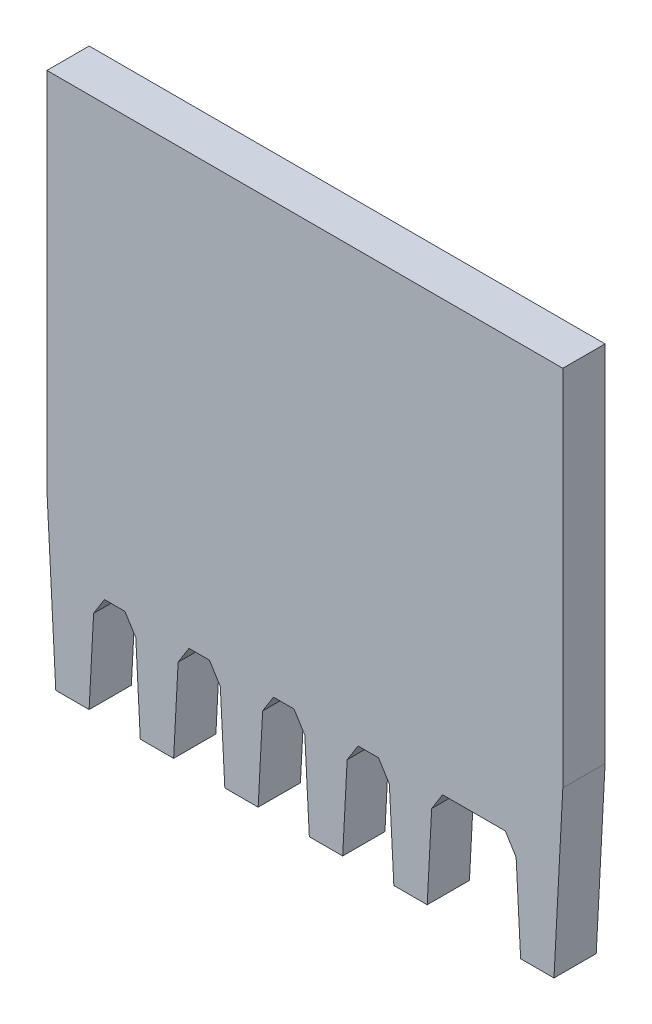
SolidWorks part; units mm, degrees
ref_plane "Front Plane" through (0, 0, 0) normal (0, 0, 1) x (1, 0, 0)
ref_plane "Top Plane" through (0, 0, 0) normal (0, 1, 0) x (1, 0, 0)
ref_plane "Right Plane" through (0, 0, 0) normal (1, 0, 0) x (0, 0, -1)
sketch "Sketch1" plane through (0, 0, 0) normal (0, 0, 1) x (1, 0, 0)
  line L0 (0, 0) -> (0, 18.9) construction
  line L1 (0, 18.9) -> (18.3124, 18.9) construction
  line L2 (18.3124, 18.9) -> (18.3124, 0) construction
  line L3 (18.3124, 0) -> (0, 0) construction
  line L4 (0, 3) -> (18.3124, 3) construction
  line L5 (0, 6) -> (18.3124, 6) construction
  line L6 (0.9062, 6) -> (0.9062, 0) construction
  line L7 (3.9062, 6) -> (3.9062, 0) construction
  line L8 (6.9062, 6) -> (6.9062, 0) construction
  line L9 (9.9062, 6) -> (9.9062, 0) construction
  line L10 (12.9062, 6) -> (12.9062, 0) construction
  line L11 (17.4062, 6) -> (17.4062, 0) construction
  line L12 (0.9062, 3) -> (3.9062, 3) construction
  line L13 (3.9062, 3) -> (6.9062, 3) construction
  line L14 (6.9062, 3) -> (9.9062, 3) construction
  line L15 (9.9062, 3) -> (12.9062, 3) construction
  line L16 (12.9062, 3) -> (17.4062, 3) construction
  line L17 (0.9062, 3) -> (0, 3) construction
  line L18 (17.4062, 3) -> (18.3124, 3) construction
  line L19 (2.4062, 3) -> (2.4062, 0) construction
  line L20 (5.4062, 3) -> (5.4062, 0) construction
  line L21 (8.4062, 3) -> (8.4062, 0) construction
  line L22 (11.4062, 3) -> (11.4062, 0) construction
  line L23 (15.1562, 3) -> (15.1562, 0) construction
  line L24 (14.4062, 3.75) -> (15.9062, 3.75) construction
  line L25 (0, 6) -> (0.3144, 0)
  line L26 (0.3144, 0) -> (1.4979, 0)
  line L27 (1.4979, 0) -> (1.6572, 3.0393)
  line L28 (3.1552, 3.0393) -> (3.3144, 0)
  line L29 (3.3144, 0) -> (4.4979, 0)
  line L30 (4.4979, 0) -> (4.6572, 3.0393)
  line L31 (6.1552, 3.0393) -> (6.3144, 0)
  line L32 (6.3144, 0) -> (7.4979, 0)
  line L33 (7.4979, 0) -> (7.6572, 3.0393)
  line L34 (9.1552, 3.0393) -> (9.3144, 0)
  line L35 (9.3144, 0) -> (10.4979, 0)
  line L36 (10.4979, 0) -> (10.6572, 3.0393)
  line L37 (12.1552, 3.0393) -> (12.3144, 0)
  line L38 (12.3144, 0) -> (13.4979, 0)
  line L39 (13.4979, 0) -> (13.6572, 3.0393)
  line L40 (16.6552, 3.0393) -> (16.8144, 0)
  line L41 (16.8144, 0) -> (17.9979, 0)
  line L42 (17.9979, 0) -> (18.3124, 6)
  line L44 (1.6572, 3.0393) -> (2.0426, 3.656)
  line L45 (0, 6) -> (0, 18.9)
  line L46 (0, 18.9) -> (18.3124, 18.9)
  line L47 (18.3124, 18.9) -> (18.3124, 6)
  line L48 (9.1562, 18.9) -> (9.1562, 6) construction
  line L49 (2.0426, 3.656) -> (2.7698, 3.656)
  line L50 (2.7698, 3.656) -> (3.1552, 3.0393)
  line L51 (4.6572, 3.0393) -> (5.0426, 3.656)
  line L52 (5.0426, 3.656) -> (5.7698, 3.656)
  line L53 (5.7698, 3.656) -> (6.1552, 3.0393)
  line L54 (7.6572, 3.0393) -> (8.0426, 3.656)
  line L55 (8.0426, 3.656) -> (8.7698, 3.656)
  line L56 (8.7698, 3.656) -> (9.1552, 3.0393)
  line L57 (10.6572, 3.0393) -> (11.0426, 3.656)
  line L58 (11.0426, 3.656) -> (11.7698, 3.656)
  line L59 (11.7698, 3.656) -> (12.1552, 3.0393)
  line L60 (13.6572, 3.0393) -> (14.0426, 3.656)
  line L61 (14.0426, 3.656) -> (16.2698, 3.656)
  line L62 (16.2698, 3.656) -> (16.6552, 3.0393)
  arc A0 (3.1552, 3.0393) -> (1.6572, 3.0393) centre (2.4062, 3) ccw construction
  arc A1 (6.1552, 3.0393) -> (4.6572, 3.0393) centre (5.4062, 3) ccw construction
  arc A2 (9.1552, 3.0393) -> (7.6572, 3.0393) centre (8.4062, 3) ccw construction
  arc A3 (12.1552, 3.0393) -> (10.6572, 3.0393) centre (11.4062, 3) ccw construction
  arc A4 (13.6572, 3.0393) -> (14.4062, 3.75) centre (14.4062, 3) cw construction
  arc A5 (16.6552, 3.0393) -> (15.9062, 3.75) centre (15.9062, 3) ccw construction
  dimension "D7" = 0.75
  dimension "D1" = 3
  dimension "D2" = 6
  dimension "D3" = 12.9
  dimension "D4" = 3
  dimension "D6" = 4.5
  dimension "D8" = 3
  dimension "D9" = 18.3124
  dimension "D10" = 18.9
extrude "Boss-Extrude1" add sketch "Sketch1" along normal blind 1.5
sketch "Sketch3" plane through (0, 0, 0) normal (0, 0, 1) x (1, 0, 0)
  line L0 (-0.4005, 6) -> (18.7129, 6)
  line L1 (18.7129, 3) -> (-0.4005, 3) construction
  line L2 (-0.4005, 0) -> (18.7129, 0) construction
  line L3 (-0.4005, -0.5) -> (18.7129, -0.5) construction
  line L4 (18.7129, -0.5) -> (18.7129, 6) construction
  line L5 (-0.4005, 6) -> (-0.4005, -0.5) construction
  line L6 (18.3124, 0) -> (0, 0) construction
  line L7 (0, 3) -> (18.3124, 3) construction
  line L8 (0, 6) -> (18.3124, 6) construction
  line L9 (0.3407, -0.5) -> (0, 6) construction
  line L10 (18.3124, 6) -> (17.9717, -0.5) construction
  line L11 (17.9979, 0) -> (18.3124, 6) construction
  line L12 (0, 6) -> (0.3144, 0) construction
  line L13 (5.4062, 6) -> (5.4062, -0.5) construction
  line L14 (3.9062, 6) -> (3.9062, -0.5) construction
  line L15 (5.4062, 3) -> (5.4062, 0) construction
  line L16 (3.1572, 3) -> (3.3407, -0.5) construction
  line L17 (2.7567, 3) -> (2.9401, -0.5)
  line L18 (3.1552, 3.0393) -> (3.3144, 0) construction
  line L19 (2.9401, -0.5) -> (4.8723, -0.5)
  line L20 (4.8723, -0.5) -> (5.0557, 3)
  line L21 (2.8484, 1.25) -> (3.2478, 1.2709) construction
  line L22 (5.9401, -0.5) -> (5.7567, 3)
  line L26 (7.8723, -0.5) -> (5.9401, -0.5)
  line L27 (8.0557, 3) -> (7.8723, -0.5)
  line L30 (2.4062, -0.5) -> (2.4062, 6) construction
  line L31 (2.4062, 3) -> (2.4062, 0) construction
  line L32 (8.4062, 6) -> (8.4062, -0.5) construction
  line L34 (11.4062, -0.5) -> (11.4062, 6) construction
  line L35 (15.1562, -0.5) -> (15.1562, 6) construction
  line L36 (8.4062, 3) -> (8.4062, 0) construction
  line L37 (11.4062, 3) -> (11.4062, 0) construction
  line L38 (15.1562, 3) -> (15.1562, 0) construction
  line L39 (10.8723, -0.5) -> (11.0557, 3)
  line L40 (8.9401, -0.5) -> (10.8723, -0.5)
  line L41 (8.7567, 3) -> (8.9401, -0.5)
  line L42 (11.9401, -0.5) -> (11.7567, 3)
  line L43 (13.8723, -0.5) -> (11.9401, -0.5)
  line L44 (14.0557, 3) -> (13.8723, -0.5)
  line L45 (16.4401, -0.5) -> (18.3723, -0.5)
  line L46 (16.2567, 3) -> (16.4401, -0.5)
  line L47 (18.3723, -0.5) -> (18.7129, 6)
  line L48 (1.8723, -0.5) -> (-0.0599, -0.5)
  line L49 (2.0557, 3) -> (1.8723, -0.5)
  line L50 (-0.0599, -0.5) -> (-0.4005, 6)
  line L51 (16.2567, 3) -> (14.0557, 3)
  line L52 (11.7567, 3) -> (11.0557, 3)
  line L53 (8.7567, 3) -> (8.0557, 3)
  line L54 (5.7567, 3) -> (5.0557, 3)
  line L55 (2.7567, 3) -> (2.0557, 3)
  dimension "D1" = 0.5
  dimension "D2" = 0.4
ref_plane "Plane1" through (3.9062, 0, 0) normal (1, 0, 0) x (0, 0, -1)
sketch "Sketch4" plane through (3.9062, 0, 0) normal (1, 0, 0) x (0, 0, -1)
  line L0 (0, 6) -> (0, -0.5) construction
  line L1 (0.6, 6) -> (-2.1, 6) construction
  line L2 (0.6, 6) -> (0.6, -0.5) construction
  line L3 (0.6, -0.5) -> (-2.1, -0.5) construction
  line L4 (-2.1, 6) -> (-2.1, -0.5) construction
  line L5 (-0.75, -0.5) -> (-0.75, 6) construction
  line L6 (-1.5, 6) -> (-1.5, -0.5) construction
  line L7 (0.6, 2.4005) -> (-2.1, 2.4005) construction
  line L8 (0.3, 6) -> (0.3, -0.5) construction
  line L9 (0.6, 2.4005) -> (3.846, 6) construction
  line L10 (2.2302, 6) -> (0.6, 4.1923) construction
  line L11 (0.6, 4.1923) -> (1.7139, 3.1878) construction
  line L12 (1.7139, 3.1878) -> (4.25, 6)
  line L13 (4.25, 6) -> (0.6, 6) construction
  line L14 (0.3, 1) -> (-1.8, 1) construction
  line L15 (-2.1, 0) -> (0.6, 0) construction
  line L16 (1.7139, 3.1878) -> (1.4912, 3.3887)
  line L17 (1.4912, 3.3887) -> (0.6, 2.4005)
  line L18 (-3.2139, 3.1878) -> (-5.75, 6)
  line L19 (-3.2139, 3.1878) -> (-2.9912, 3.3887)
  line L20 (-2.9912, 3.3887) -> (-2.1, 2.4005)
  line L21 (-2.1, 6) -> (-5.75, 6) construction
  line L22 (0.6, 3.0724) -> (3.2401, 6) construction
  arc A0 (0.4965, 2.2224) -> (0.6, -0.5) centre (4.2, 1) ccw
  arc A1 (0.6, 2.4005) -> (0.4965, 2.2224) centre (0.9713, 2.0656) ccw
  arc A2 (-2.1, 2.4005) -> (-1.9965, 2.2224) centre (-2.4713, 2.0656) cw
  arc A3 (-1.9965, 2.2224) -> (-2.1, -0.5) centre (-5.7, 1) cw
  dimension "D6" = 0.5
  dimension "D1" = 0.6
  dimension "D2" = 0.3
  dimension "D3" = 1.5
  dimension "D4" = 1
  dimension "D5" = 0.3
  dimension "D7" = 10
sketch "Sketch5" plane through (0, 0, 0) normal (1, 0, 0) x (0, 0, -1)
  line L0 (2.2302, 6) -> (0.6, 4.1923) construction
  line L1 (0.6, 4.1923) -> (1.7139, 3.1878) construction
  line L2 (1.7139, 3.1878) -> (4.25, 6) construction
  line L3 (2.2302, 6) -> (0.6, 4.1923) construction
  line L4 (0.6, 4.1923) -> (1.7139, 3.1878) construction
  line L5 (1.7139, 3.1878) -> (4.25, 6) construction
ref_plane "Plane2" through (0, 2.6105, -2.3541) normal (0, 0.7426, -0.6697) x (1, 0, 0)
sketch "Sketch6" plane through (0, 2.6105, -2.3541) normal (0, 0.7426, -0.6697) x (1, 0, 0)
  line L1 (3.9062, -2.362) -> (3.9062, -0.862) construction
  line L2 (3.9062, -2.362) -> (3.9062, -5.0612) construction
  line L3 (4.6562, -5.0612) -> (3.1562, -5.0612)
  line L4 (4.6562, -1.612) -> (3.1562, -1.612) construction
  line L5 (3.1562, -1.612) -> (3.1562, -5.0612)
  line L6 (4.6562, -1.612) -> (4.6562, -5.0612)
  line L10 (2.4062, -5.0612) -> (15.1562, -5.0612) construction
  line L11 (15.1562, -5.0612) -> (15.1562, -0.862) construction
  line L12 (15.1562, -0.862) -> (2.4062, -0.862) construction
  line L13 (2.4062, -0.862) -> (2.4062, -5.0612) construction
  line L14 (15.1562, 0.3349) -> (15.1562, -4.0182) construction
  line L15 (2.4062, 0.3349) -> (2.4062, -4.0182) construction
  line L16 (11.4062, -5.0612) -> (11.4062, -0.862) construction
  line L17 (8.4062, -5.0612) -> (8.4062, -0.862) construction
  line L18 (5.4062, -5.0612) -> (5.4062, -0.862) construction
  line L19 (5.4062, -4.0182) -> (5.4062, 0.3349) construction
  line L20 (8.4062, -4.0182) -> (8.4062, 0.3349) construction
  line L21 (11.4062, 0.3349) -> (11.4062, -4.0182) construction
  line L22 (0.1562, -1.612) -> (0.1562, -5.0612)
  line L23 (0.1562, -5.0612) -> (1.6562, -5.0612)
  line L24 (1.6562, -1.612) -> (1.6562, -5.0612)
  line L25 (7.6562, -1.612) -> (7.6562, -5.0612)
  line L26 (6.1562, -5.0612) -> (7.6562, -5.0612)
  line L27 (6.1562, -1.612) -> (6.1562, -5.0612)
  line L28 (10.6562, -1.612) -> (10.6562, -5.0612)
  line L29 (10.6562, -5.0612) -> (9.1562, -5.0612)
  line L30 (9.1562, -1.612) -> (9.1562, -5.0612)
  line L31 (13.6562, -1.612) -> (13.6562, -5.0612)
  line L32 (12.1562, -5.0612) -> (13.6562, -5.0612)
  line L33 (12.1562, -1.612) -> (12.1562, -5.0612)
  line L34 (18.1562, -1.612) -> (18.1562, -5.0612)
  line L35 (18.1562, -5.0612) -> (16.6562, -5.0612)
  line L36 (16.6562, -1.612) -> (16.6562, -5.0612)
  circle A0 centre (3.9062, -1.612) radius 0.75 construction
  arc A1 (4.6562, -1.612) -> (3.1562, -1.612) centre (3.9062, -1.612) ccw
  arc A2 (0.1562, -1.612) -> (1.6562, -1.612) centre (0.9062, -1.612) cw
  arc A3 (6.1562, -1.612) -> (7.6562, -1.612) centre (6.9062, -1.612) cw
  arc A4 (10.6562, -1.612) -> (9.1562, -1.612) centre (9.9062, -1.612) ccw
  arc A5 (12.1562, -1.612) -> (13.6562, -1.612) centre (12.9062, -1.612) cw
  arc A6 (18.1562, -1.612) -> (16.6562, -1.612) centre (17.4062, -1.612) ccw
ref_plane "Plane3" through (0, 1.6223, -1.463) normal (0, 0.7426, -0.6697) x (1, 0, 0)
sketch "Sketch7" plane through (0, 1.6223, -1.463) normal (0, 0.7426, -0.6697) x (1, 0, 0)
  line L0 (3.1562, -1.612) -> (3.1562, -5.0612) construction
  line L1 (4.6562, -5.0612) -> (3.1562, -5.0612) construction
  line L2 (4.6562, -1.612) -> (4.6562, -5.0612) construction
  line L3 (3.1562, -1.612) -> (3.1562, -5.0612) construction
  line L4 (4.6562, -5.0612) -> (3.1562, -5.0612) construction
  line L5 (4.6562, -1.612) -> (4.6562, -5.0612) construction
  line L6 (3.9062, -0.862) -> (3.9062, -5.0612) construction
  line L7 (4.6562, -1.612) -> (3.1562, -1.612) construction
  line L8 (4.6562, -2.362) -> (3.1562, -2.362) construction
  line L9 (3.4562, -1.612) -> (3.4562, -2.362)
  line L10 (3.4562, -2.362) -> (4.3562, -2.362)
  line L11 (4.3562, -2.362) -> (4.3562, -1.612)
  line L12 (2.4062, -0.862) -> (2.4062, -5.0612) construction
  line L13 (2.4062, -5.0612) -> (15.1562, -5.0612) construction
  line L14 (15.1562, -0.862) -> (2.4062, -0.862) construction
  line L15 (5.4062, -5.0612) -> (5.4062, -0.862) construction
  line L16 (8.4062, -5.0612) -> (8.4062, -0.862) construction
  line L17 (11.4062, -5.0612) -> (11.4062, -0.862) construction
  line L18 (15.1562, -5.0612) -> (15.1562, -0.862) construction
  line L19 (2.4062, -0.862) -> (2.4062, -5.0612) construction
  line L20 (2.4062, -5.0612) -> (15.1562, -5.0612) construction
  line L21 (15.1562, -0.862) -> (2.4062, -0.862) construction
  line L22 (5.4062, -5.0612) -> (5.4062, -0.862) construction
  line L23 (8.4062, -5.0612) -> (8.4062, -0.862) construction
  line L24 (11.4062, -5.0612) -> (11.4062, -0.862) construction
  line L25 (15.1562, -5.0612) -> (15.1562, -0.862) construction
  line L26 (0.4562, -2.362) -> (0.4562, -1.612)
  line L27 (1.3562, -2.362) -> (0.4562, -2.362)
  line L28 (1.3562, -1.612) -> (1.3562, -2.362)
  line L29 (7.3562, -2.362) -> (6.4562, -2.362)
  line L30 (7.3562, -1.612) -> (7.3562, -2.362)
  line L31 (6.4562, -2.362) -> (6.4562, -1.612)
  line L32 (9.4562, -1.612) -> (9.4562, -2.362)
  line L33 (10.3562, -2.362) -> (10.3562, -1.612)
  line L34 (9.4562, -2.362) -> (10.3562, -2.362)
  line L35 (13.3562, -1.612) -> (13.3562, -2.362)
  line L36 (12.4562, -2.362) -> (12.4562, -1.612)
  line L37 (13.3562, -2.362) -> (12.4562, -2.362)
  line L38 (16.9562, -1.612) -> (16.9562, -2.362)
  line L39 (17.8562, -2.362) -> (17.8562, -1.612)
  line L40 (16.9562, -2.362) -> (17.8562, -2.362)
  arc A0 (4.6562, -1.612) -> (3.1562, -1.612) centre (3.9062, -1.612) ccw construction
  arc A1 (4.6562, -1.612) -> (3.1562, -1.612) centre (3.9062, -1.612) ccw construction
  circle A2 centre (3.9062, -1.612) radius 0.45 construction
  arc A3 (4.3562, -1.612) -> (3.4562, -1.612) centre (3.9062, -1.612) ccw
  arc A4 (0.4562, -1.612) -> (1.3562, -1.612) centre (0.9062, -1.612) cw
  arc A5 (6.4562, -1.612) -> (7.3562, -1.612) centre (6.9062, -1.612) cw
  arc A6 (10.3562, -1.612) -> (9.4562, -1.612) centre (9.9062, -1.612) ccw
  arc A7 (12.4562, -1.612) -> (13.3562, -1.612) centre (12.9062, -1.612) cw
  arc A8 (17.8562, -1.612) -> (16.9562, -1.612) centre (17.4062, -1.612) ccw
ref_plane "bisect" through (0, 0, 0.75) normal (0, 0, 1) x (1, 0, 0)
ref_plane "insert_surface" through (0, 6, 0) normal (0, 1, 0) x (1, 0, 0)
sketch "Sketch8" plane through (0, 6, 0) normal (0, 1, 0) x (1, 0, 0)
  line L0 (18.7129, -0.75) -> (-0.4005, -0.75) construction
  line L1 (-0.4005, 0.6) -> (18.7129, 0.6)
  line L2 (-0.4005, 0.6) -> (-0.4005, -2.1)
  line L3 (-0.4005, -2.1) -> (18.7129, -2.1)
  line L4 (18.7129, 0.6) -> (18.7129, -2.1)
  line L5 (9.1562, 0.6) -> (9.1562, -2.1) construction
  line L6 (0, 0) -> (18.3124, 0) construction
  line L7 (0, 0) -> (0, -1.5) construction
  line L8 (0, -1.5) -> (18.3124, -1.5) construction
  line L9 (18.3124, 0) -> (18.3124, -1.5) construction
  line L10 (18.7129, 0.3) -> (-0.4005, 0.3) construction
  line L11 (18.7129, -1.8) -> (-0.4005, -1.8) construction
sketch "Sketch9" plane through (0, 0, 0) normal (0, 0, 1) x (1, 0, 0)
  line L0 (18.3723, -0.5) -> (18.7129, 6) construction
  line L1 (-0.4005, 6) -> (18.7129, 6) construction
  line L2 (-0.0599, -0.5) -> (-0.4005, 6) construction
  line L3 (1.8723, -0.5) -> (-0.0599, -0.5) construction
  line L4 (2.0557, 3) -> (1.8723, -0.5) construction
  line L5 (2.7567, 3) -> (2.0557, 3) construction
  line L6 (2.7567, 3) -> (2.9401, -0.5) construction
  line L7 (2.9401, -0.5) -> (4.8723, -0.5) construction
  line L8 (4.8723, -0.5) -> (5.0557, 3) construction
  line L9 (5.7567, 3) -> (5.0557, 3) construction
  line L10 (5.9401, -0.5) -> (5.7567, 3) construction
  line L11 (7.8723, -0.5) -> (5.9401, -0.5) construction
  line L12 (8.0557, 3) -> (7.8723, -0.5) construction
  line L13 (8.7567, 3) -> (8.0557, 3) construction
  line L14 (8.7567, 3) -> (8.9401, -0.5) construction
  line L15 (8.9401, -0.5) -> (10.8723, -0.5) construction
  line L16 (10.8723, -0.5) -> (11.0557, 3) construction
  line L17 (11.7567, 3) -> (11.0557, 3) construction
  line L18 (11.9401, -0.5) -> (11.7567, 3) construction
  line L19 (13.8723, -0.5) -> (11.9401, -0.5) construction
  line L20 (14.0557, 3) -> (13.8723, -0.5) construction
  line L21 (16.2567, 3) -> (14.0557, 3) construction
  line L22 (16.2567, 3) -> (16.4401, -0.5) construction
  line L23 (16.4401, -0.5) -> (18.3723, -0.5) construction
  line L24 (18.3723, -0.5) -> (18.7129, 6)
  line L25 (-0.4005, 6) -> (18.7129, 6) construction
  line L26 (-0.0599, -0.5) -> (-0.4005, 6)
  line L27 (1.8723, -0.5) -> (-0.0599, -0.5)
  line L28 (2.0557, 3) -> (1.8723, -0.5)
  line L29 (2.7567, 3) -> (2.0557, 3) construction
  line L30 (2.7567, 3) -> (2.9401, -0.5)
  line L31 (2.9401, -0.5) -> (4.8723, -0.5)
  line L32 (4.8723, -0.5) -> (5.0557, 3)
  line L33 (5.7567, 3) -> (5.0557, 3) construction
  line L34 (5.9401, -0.5) -> (5.7567, 3)
  line L35 (7.8723, -0.5) -> (5.9401, -0.5)
  line L36 (8.0557, 3) -> (7.8723, -0.5)
  line L37 (8.7567, 3) -> (8.0557, 3) construction
  line L38 (8.7567, 3) -> (8.9401, -0.5)
  line L39 (8.9401, -0.5) -> (10.8723, -0.5)
  line L40 (10.8723, -0.5) -> (11.0557, 3)
  line L41 (11.7567, 3) -> (11.0557, 3) construction
  line L42 (11.9401, -0.5) -> (11.7567, 3)
  line L43 (13.8723, -0.5) -> (11.9401, -0.5)
  line L44 (14.0557, 3) -> (13.8723, -0.5)
  line L45 (16.2567, 3) -> (14.0557, 3) construction
  line L46 (16.2567, 3) -> (16.4401, -0.5)
  line L47 (16.4401, -0.5) -> (18.3723, -0.5)
  line L48 (16.2567, 3) -> (16.2567, 6)
  line L49 (14.0557, 3) -> (14.0557, 6)
  line L50 (11.7567, 3) -> (11.7567, 6)
  line L51 (18.7129, 6) -> (-0.4005, 6) construction
  line L52 (11.0557, 3) -> (11.0557, 6)
  line L53 (-0.4005, 6) -> (18.7129, 6) construction
  line L54 (8.7567, 3) -> (8.7567, 6)
  line L55 (8.0557, 3) -> (8.0557, 6)
  line L58 (5.7567, 3) -> (5.7567, 6)
  line L60 (5.0557, 3) -> (5.0557, 6)
  line L62 (15.1562, -0.5) -> (15.1562, 6) construction
  line L63 (15.1562, -0.5) -> (15.1562, 6) construction
  line L64 (2.7567, 3) -> (2.7567, 6)
  line L65 (2.0557, 3) -> (2.0557, 6)
  line L67 (18.7129, 6) -> (16.2567, 6)
  line L68 (14.0557, 6) -> (11.7567, 6)
  line L69 (11.0557, 6) -> (8.7567, 6)
  line L70 (8.0557, 6) -> (5.7567, 6)
  line L71 (5.0557, 6) -> (2.7567, 6)
  line L72 (2.0557, 6) -> (-0.4005, 6)
sketch "Sketch10" plane through (0, 6, 0) normal (0, 1, 0) x (1, 0, 0)
  line L0 (9.1562, -0.75) -> (9.1562, -5.75) construction
  line L1 (-0.8438, 4.25) -> (19.1562, 4.25)
  line L2 (-0.8438, 4.25) -> (-0.8438, -5.75)
  line L3 (-0.8438, -5.75) -> (19.1562, -5.75)
  line L4 (19.1562, 4.25) -> (19.1562, -5.75)
  line L6 (9.1562, -0.75) -> (9.1562, 4.25) construction
  line L7 (9.1562, -0.75) -> (19.1562, -0.75) construction
  line L8 (9.1562, -0.75) -> (-0.8438, -0.75) construction
  line L9 (-10.5124, -0.75) -> (10.5124, -0.75) construction
  dimension "D1" = 20
  dimension "D2" = 10
